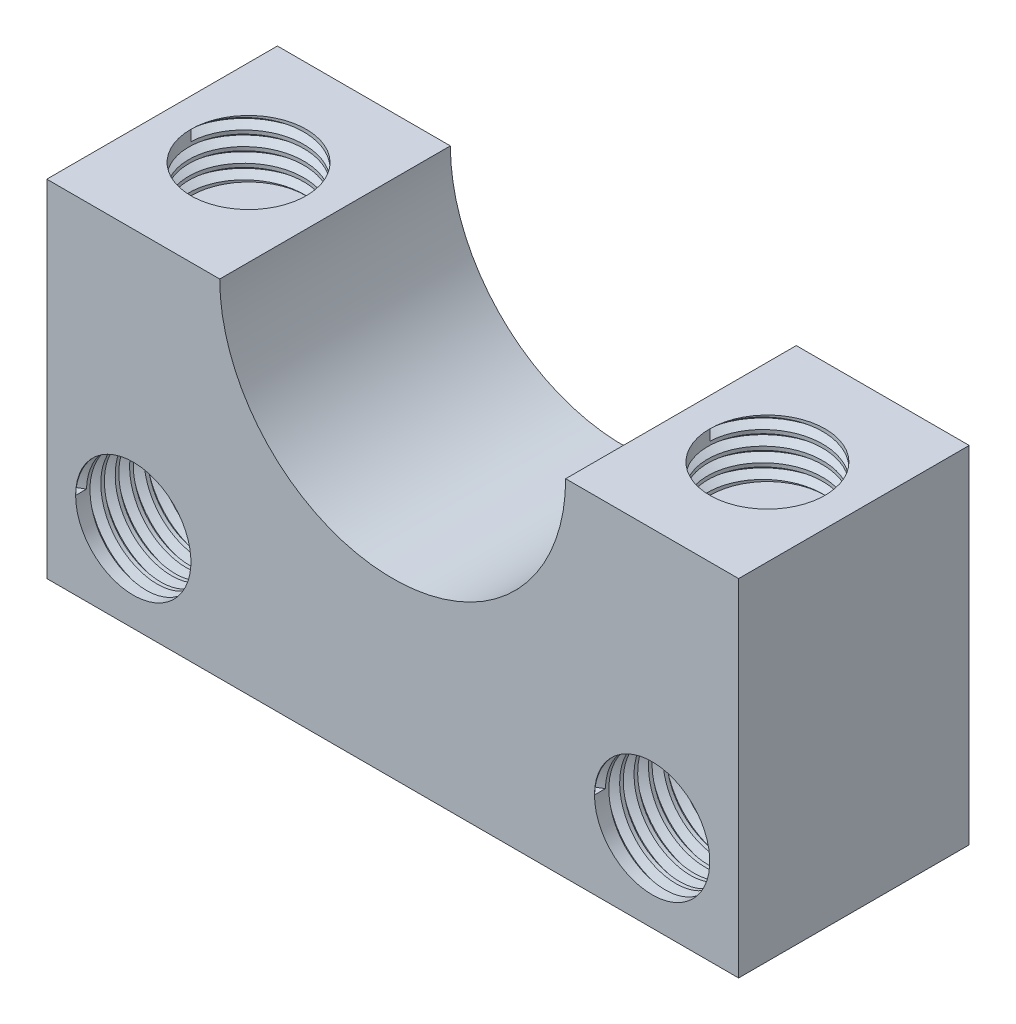
SolidWorks part; units mm, degrees
ref_plane "Front Plane" through (0, 0, 0) normal (0, 0, 1) x (1, 0, 0)
ref_plane "Top Plane" through (0, 0, 0) normal (0, 1, 0) x (1, 0, 0)
ref_plane "Right Plane" through (0, 0, 0) normal (1, 0, 0) x (0, 0, -1)
sketch "Sketch1" plane through (0, 0, 0) normal (0, 0, 1) x (1, 0, 0)
  line L1 (-6, -3) -> (6, -3)
  line L2 (-6, -3) -> (-6, 3)
  line L3 (-6, 3) -> (6, 3)
  line L4 (6, -3) -> (6, 3)
  line L5 (-6, -3) -> (6, 3) construction
  line L6 (-6, 3) -> (6, -3) construction
  point P0 (0, 0)
  dimension "D1" = 12
  dimension "D2" = 6
sketch "Sketch2" plane through (0, 0, 0) normal (0, 0, 1) x (1, 0, 0)
  line L0 (0, 0) -> (0, 3) construction
  line L1 (-6, 3) -> (6, 3) construction
  line L2 (-3, 3) -> (3, 3)
  arc A0 (-3, 3) -> (3, 3) centre (0, 3) ccw
  point P9 (0, 3)
sketch "Sketch3" plane through (0, 0, 0) normal (0, 0, 1) x (1, 0, 0)
  line L0 (0, 0) -> (0, -1.5) construction
  line L1 (-4.5, -1.5) -> (4.5, -1.5) construction
  circle A1 centre (4.5, -1.5) radius 1
  circle A2 centre (-4.5, -1.5) radius 1
  point P7 (0, -1.5)
extrude "Boss-Extrude1" add sketch "Sketch1" against normal blind 4
extrude "Cut-Extrude1" cut sketch "Sketch2" against normal blind 4
sketch "Sketch4" plane through (0, 0, 0) normal (0, 1, 0) x (1, 0, 0)
  line L0 (4.5, 0) -> (-4.5, 0) construction
  line L2 (-3, 0) -> (-6, 0) construction
  line L3 (-4.5, 0) -> (-4.5, 2) construction
  line L4 (4.5, 0) -> (4.5, 2) construction
  circle A0 centre (-4.5, 2) radius 1
  circle A1 centre (4.5, 2) radius 1
  point P4 (0, 0)
extrude "Cut-Extrude3" cut sketch "Sketch4" along normal blind 1 from offset 2
thread "Thread1" pitch 0.25 method cut profile "Thread Profile1" start angle 0, offset 0, length 1, pitch 0.25, diameter 2
ref_plane "Plane1" through (3.5, 3, -2) normal (0, 0, 1) x (-1, 0, 0)
sketch "Thread Profile1" plane through (3.5, 3, -2) normal (0, 0, 1) x (-1, 0, 0)
  line L0 (0, 0) -> (0, 0.25) construction
  line L1 (0, 0) -> (0.1353, 0.0781)
  line L2 (0.1353, 0.0781) -> (0.1353, 0.1094)
  line L3 (0.1353, 0.1094) -> (0, 0.1875)
  line L4 (0.1353, 0.0937) -> (0, 0.0937) construction
  line L11 (0, 0) -> (0, 0.1875)
  point P2 (0, 0)
  dimension "Pitch" = 0.25
  dimension "Profile_Angle" = 60
  dimension "Profile_Land" = 0.0312
  dimension "Profile_Height" = 0.1353
thread "Thread2" pitch 0.25 method cut profile "Thread Profile2" start angle 0, offset 0, length 1, pitch 0.25, diameter 2
ref_plane "Plane2" through (-5.5, 3, -2) normal (0, 0, 1) x (-1, 0, 0)
sketch "Thread Profile2" plane through (-5.5, 3, -2) normal (0, 0, 1) x (-1, 0, 0)
  line L0 (0, 0) -> (0, 0.25) construction
  line L1 (0, 0) -> (0.1353, 0.0781)
  line L2 (0.1353, 0.0781) -> (0.1353, 0.1094)
  line L3 (0.1353, 0.1094) -> (0, 0.1875)
  line L4 (0.1353, 0.0937) -> (0, 0.0937) construction
  line L11 (0, 0) -> (0, 0.1875)
  point P2 (0, 0)
  dimension "Pitch" = 0.25
  dimension "Profile_Angle" = 60
  dimension "Profile_Land" = 0.0312
  dimension "Profile_Height" = 0.1353
extrude "Cut-Extrude5" cut sketch "Sketch3" against normal blind 4
thread "Thread3" pitch 0.25 method cut profile "Thread Profile5" start angle 0, offset 0, length 4, pitch 0.25, diameter 2
ref_plane "Plane4" through (-5.5, -1.5, 0) normal (0, -1, 0) x (-1, 0, 0)
sketch "Thread Profile5" plane through (-5.5, -1.5, 0) normal (0, -1, 0) x (-1, 0, 0)
  line L0 (0, 0) -> (0, 0.25) construction
  line L1 (0, 0) -> (0.1353, 0.0781)
  line L2 (0.1353, 0.0781) -> (0.1353, 0.1094)
  line L3 (0.1353, 0.1094) -> (0, 0.1875)
  line L4 (0.1353, 0.0937) -> (0, 0.0937) construction
  line L11 (0, 0) -> (0, 0.1875)
  point P2 (0, 0)
  dimension "Pitch" = 0.25
  dimension "Profile_Angle" = 60
  dimension "Profile_Land" = 0.0312
  dimension "Profile_Height" = 0.1353
thread "Thread4" pitch 0.25 method cut profile "Thread Profile6" start angle 0, offset 0, length 4, pitch 0.25, diameter 2
ref_plane "Plane5" through (3.5, -1.5, 0) normal (0, -1, 0) x (-1, 0, 0)
sketch "Thread Profile6" plane through (3.5, -1.5, 0) normal (0, -1, 0) x (-1, 0, 0)
  line L0 (0, 0) -> (0, 0.25) construction
  line L1 (0, 0) -> (0.1353, 0.0781)
  line L2 (0.1353, 0.0781) -> (0.1353, 0.1094)
  line L3 (0.1353, 0.1094) -> (0, 0.1875)
  line L4 (0.1353, 0.0937) -> (0, 0.0937) construction
  line L11 (0, 0) -> (0, 0.1875)
  point P2 (0, 0)
  dimension "Pitch" = 0.25
  dimension "Profile_Angle" = 60
  dimension "Profile_Land" = 0.0312
  dimension "Profile_Height" = 0.1353
